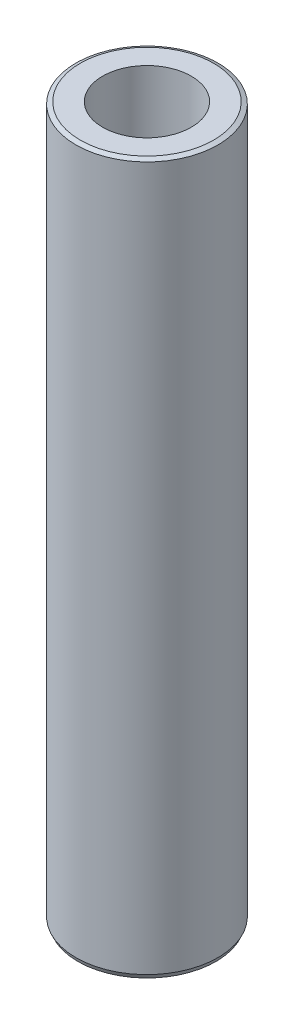
SolidWorks part; units mm, degrees
ref_plane "Front Plane" through (0, 0, 0) normal (0, 0, 1) x (1, 0, 0)
ref_plane "Top Plane" through (0, 0, 0) normal (0, 1, 0) x (1, 0, 0)
ref_plane "Right Plane" through (0, 0, 0) normal (1, 0, 0) x (0, 0, -1)
sketch "Sketch1" plane through (0, 0, 0) normal (0, 1, 0) x (1, 0, 0)
  circle A0 centre (0, 0) radius 60
  dimension "SHAFT_OD" = 120
extrude "Boss-Extrude1" add sketch "Sketch1" along normal blind 600
sketch "Sketch2" plane through (0, 0, 0) normal (0, 1, 0) x (1, 0, 0)
  circle A0 centre (0, 0) radius 37.449
  dimension "BORE_D" = 74.898
extrude "Cut-Extrude1" cut sketch "Sketch2" along normal through all
chamfer "Chamfer1" distance 1.6762 angle 65.504 2 edges at (0, 600, 60) (0, 0, 60) first distance on face at (0, 600, 60) first distance on face at (0, 0, 37.449)
